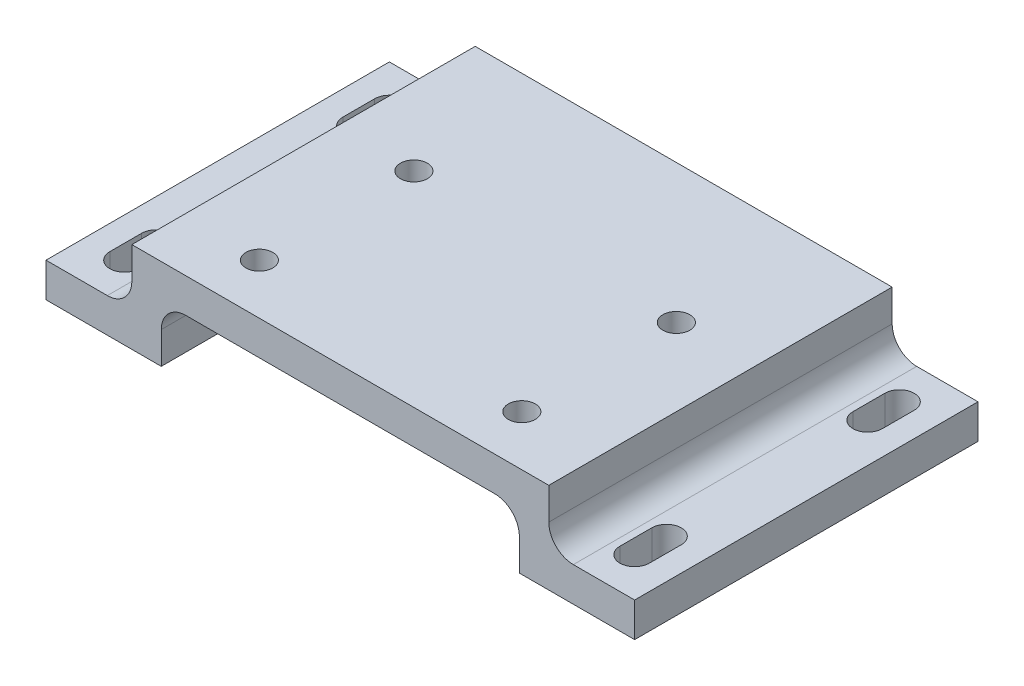
SolidWorks part; units mm, degrees
ref_plane "Front Plane" through (0, 0, 0) normal (0, 0, 1) x (1, 0, 0)
ref_plane "Top Plane" through (0, 0, 0) normal (0, 1, 0) x (1, 0, 0)
ref_plane "Right Plane" through (0, 0, 0) normal (1, 0, 0) x (0, 0, -1)
sketch "Sketch1" plane through (0, 0, 0) normal (0, 0, 1) x (1, 0, 0)
  line L0 (-60, -11.5) -> (-36.5, -11.5)
  line L1 (-36.5, -11.5) -> (-36.5, 0)
  line L2 (-36.5, 0) -> (36.5, 0)
  line L3 (36.5, 0) -> (36.5, -11.5)
  line L4 (36.5, -11.5) -> (60, -11.5)
  line L5 (60, -11.5) -> (60, -4.5)
  line L6 (60, -4.5) -> (42.5, -4.5)
  line L7 (42.5, -4.5) -> (42.5, 7)
  line L8 (42.5, 7) -> (-42.5, 7)
  line L9 (-42.5, 7) -> (-42.5, -4.5)
  line L10 (-42.5, -4.5) -> (-60, -4.5)
  line L11 (-60, -4.5) -> (-60, -11.5)
  dimension "D1" = 23.5
  dimension "D2" = 85
  dimension "D3" = 120
  dimension "D4" = 7
  dimension "D5" = 7
  dimension "D6" = 18.5
extrude "Boss-Extrude1" add sketch "Sketch1" along normal blind 35 and the other way blind 35
fillet "Fillet1" radius 5 4 edges at (36.5, 0, 0) (-36.5, 0, 0) (-42.5, -4.5, 0) (42.5, -4.5, 0)
sketch "Sketch2" plane through (0, 0, 0) normal (0, 1, 0) x (1, 0, 0)
  line L0 (-26.75, 6.75) -> (26.75, 6.75) construction
  line L1 (26.75, 6.75) -> (26.75, -24.75) construction
  line L2 (26.75, -24.75) -> (-26.75, -24.75) construction
  line L3 (-26.75, -24.75) -> (-26.75, 6.75) construction
  line L4 (0, 0) -> (0, 6.75) construction
  line L5 (42.5, 35) -> (-42.5, 35) construction
  line L7 (-52, 27) -> (52, 27) construction
  line L8 (52, 27) -> (52, 20.5) construction
  line L9 (52, 20.5) -> (-52, 20.5) construction
  line L10 (-52, 20.5) -> (-52, 27) construction
  line L11 (-52, -27) -> (52, -27) construction
  line L12 (52, -27) -> (52, -20.5) construction
  line L13 (52, -20.5) -> (-52, -20.5) construction
  line L14 (-52, -20.5) -> (-52, -27) construction
  line L15 (-52, 20.5) -> (-52, -20.5) construction
  line L16 (52, -20.5) -> (52, 20.5) construction
  line L17 (-55, -20.5) -> (-55, -27)
  line L18 (-49, -27) -> (-49, -20.5)
  line L19 (55, -20.5) -> (55, -27)
  line L20 (49, -27) -> (49, -20.5)
  line L21 (55, 27) -> (55, 20.5)
  line L22 (49, 27) -> (49, 20.5)
  line L23 (-55, 27) -> (-55, 20.5)
  line L24 (-49, 20.5) -> (-49, 27)
  line L25 (-52, 0) -> (0, 0) construction
  line L26 (0, 0) -> (0, 27) construction
  line L27 (-52, 27) -> (-52, 30) construction
  line L28 (-52, 30) -> (-52, 35) construction
  line L29 (-47.5, 35) -> (-60, 35) construction
  line L30 (-60, 35) -> (-60, -35) construction
  circle A0 centre (-26.75, 6.75) radius 2.75
  circle A1 centre (-26.75, -24.75) radius 2.75
  circle A2 centre (26.75, 6.75) radius 2.75
  circle A3 centre (26.75, -24.75) radius 2.75
  circle A4 centre (52, 27) radius 3
  circle A5 centre (52, 20.5) radius 3
  circle A6 centre (52, -20.5) radius 3
  circle A7 centre (52, -27) radius 3
  circle A8 centre (-52, -20.5) radius 3
  circle A9 centre (-52, -27) radius 3
  circle A10 centre (-52, 27) radius 3
  circle A11 centre (-52, 20.5) radius 3
  dimension "D1" = 5.5
  dimension "D5" = 6
  dimension "D2" = 53.5
  dimension "D3" = 31.5
  dimension "D4" = 28.25
  dimension "D6" = 6.5
  dimension "D7" = 5
  dimension "D8" = 5
extrude "Cut-Extrude1" cut sketch "Sketch2" against normal through all both and the other way through all contours A10 | A11 L24 A10 L23 | A11 | A8 | A9 L18 A8 L17 | A9 | A6 | A7 L19 A6 L20 | A7 | A4 | A5 L21 A4 L22 | A5 | A0 | A2 | A3 | A1 region at (-52, 0, 23.75) region at (-52, 0, 20.5) region at (-52, 0, 27) region at (52, 0, 20.5) region at (52, 0, 23.75) region at (52, 0, 27) region at (52, 0, -27) region at (52, 0, -23.75) region at (52, 0, -20.5) region at (-52, 0, -23.75) region at (-52, 0, -27) region at (-52, 0, -20.5) region at (-26.75, 0, -6.75) region at (-26.75, 0, 24.75) region at (26.75, 0, -6.75) region at (26.75, 0, 24.75)
